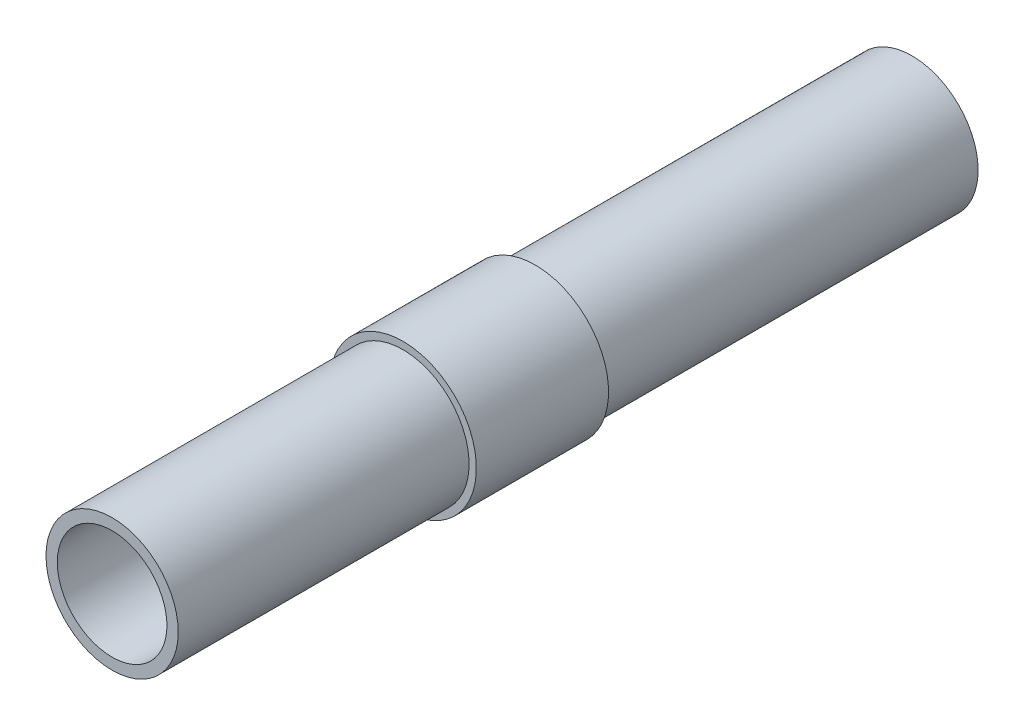
SolidWorks part; units mm, degrees
ref_plane "Front Plane" through (0, 0, 0) normal (0, 0, 1) x (1, 0, 0)
ref_plane "Top Plane" through (0, 0, 0) normal (0, 1, 0) x (1, 0, 0)
ref_plane "Right Plane" through (0, 0, 0) normal (1, 0, 0) x (0, 0, -1)
sketch "Sketch1" plane through (0, 0, 0) normal (0, 0, 1) x (1, 0, 0)
  circle A0 centre (0, 0) radius 11.1
  circle A1 centre (0, 0) radius 7.9 construction
  dimension "D1" = 22.2
  dimension "D2" = 15.8
extrude "Boss-Extrude1" add sketch "Sketch1" along normal blind 58
sketch "Sketch2" plane through (0, 0, 0) normal (0, 0, -1) x (-1, 0, 0)
  circle A0 centre (0, 0) radius 10
  circle A1 centre (0, 0) radius 24.7779
  dimension "D1" = 20
extrude "Cut-Extrude1" cut sketch "Sketch2" against normal blind 24
extrude "Cut-Extrude2" cut sketch "Sketch2<2>" against normal blind 14 from offset 44 offset against normal yes
sketch "Sketch2<2>" plane through (0, 0, 0) normal (0, 0, -1) x (-1, 0, 0) same geometry as "Sketch2"
sketch "Sketch4" plane through (0, 0, 58) normal (0, 0, 1) x (1, 0, 0)
  circle A0 centre (0, 0) radius 10
extrude "Boss-Extrude3" add sketch "Sketch4" along normal blind 30
sketch "Sketch5" plane through (0, 0, 0) normal (0, 0, -1) x (-1, 0, 0)
  circle A0 centre (0, 0) radius 10
extrude "Boss-Extrude4" add sketch "Sketch5" along normal blind 45
sketch "Sketch6" plane through (0, 0, -45) normal (0, 0, -1) x (-1, 0, 0)
  circle A0 centre (0, 0) radius 10
extrude "Cut-Extrude3" cut sketch "Sketch6" against normal blind 12
sketch "Sketch7" plane through (0, 0, -33) normal (0, 0, -1) x (-1, 0, 0)
  circle A0 centre (0, 0) radius 8.2874
extrude "Cut-Extrude4" cut sketch "Sketch7" against normal through all
